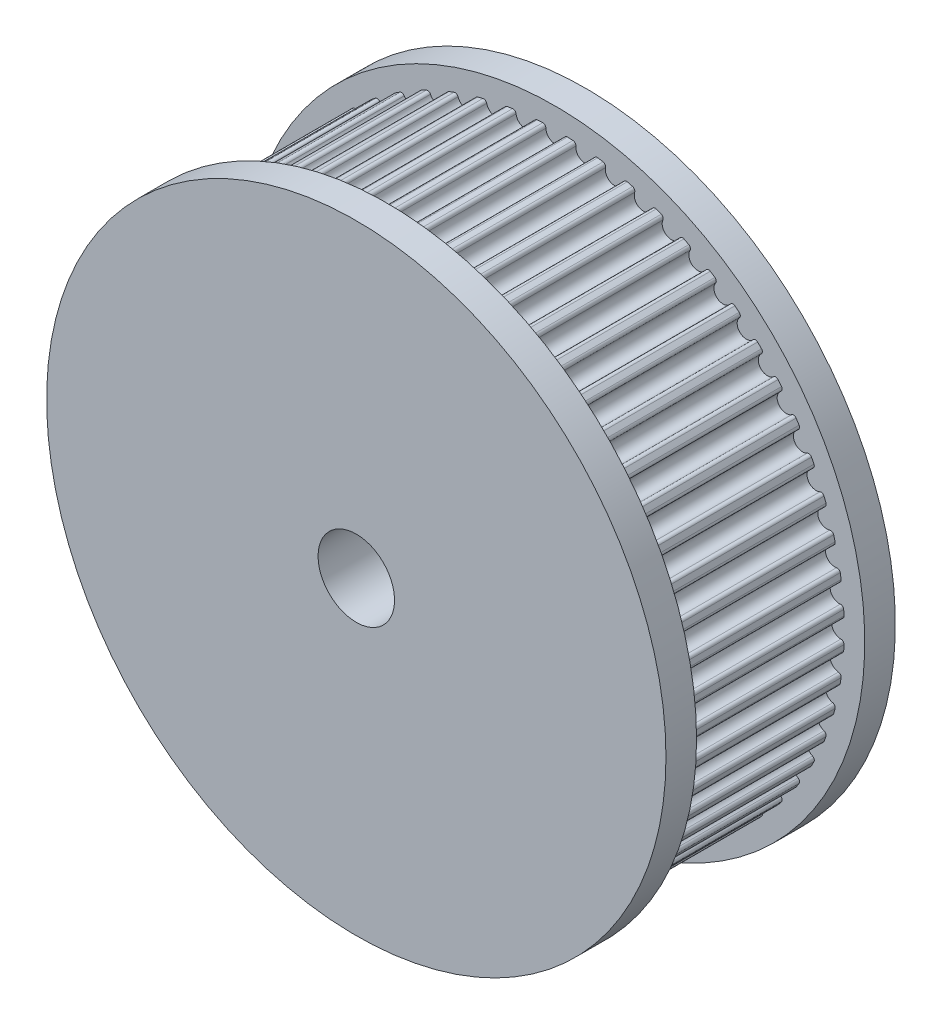
SolidWorks part; units mm, degrees
ref_plane "Front Plane" through (0, 0, 0) normal (0, 0, 1) x (1, 0, 0)
ref_plane "Top Plane" through (0, 0, 0) normal (0, 1, 0) x (1, 0, 0)
ref_plane "Right Plane" through (0, 0, 0) normal (1, 0, 0) x (0, 0, -1)
ref_axis "Axis1" through (0, 0, 55) along (0, 0, -1)
sketch "SketchRevolveGearBelt02" plane through (0, 0, 0) normal (1, 0, 0) x (0, 0, -1)
  line L0 (0, 0) -> (1, 0) construction
  line L1 (5.5, 0) -> (5.5, 18.9081)
  line L2 (5.5, 18.9081) -> (-5.5, 18.9081)
  line L3 (-5.5, 18.9081) -> (-5.5, 0)
  line L4 (-5.5, 0) -> (5.5, 0)
  dimension "GearBeltSide1" = 5.5
  dimension "GearBeltOutsideDiameter" = 18.9081
  dimension "GearBeltSide2" = 5.5
revolve "GearBelt02" add sketch "SketchRevolveGearBelt02" angle 360 about L0
sketch "SketchToothGearBelt02" plane through (0, 0, 0) normal (0, 0, 1) x (1, 0, 0)
  line L0 (-0.8105, 18.8907) -> (0, 21.4481)
  line L1 (0, 21.4481) -> (0.8105, 18.8907)
  arc A0 (0.8105, 18.8907) -> (0.6, 18.6891) centre (0.8018, 18.6891) ccw
  arc A1 (0.6, 18.6891) -> (-0.6, 18.6891) centre (0, 18.6891) cw
  arc A2 (-0.6, 18.6891) -> (-0.8105, 18.8907) centre (-0.8018, 18.6891) ccw
  dimension "GearBeltToothR1" = 0.4036
  dimension "GearBeltToothR2" = 1.2
  dimension "GearBeltToothCapX1" = 0.8105
  dimension "GearBeltToothCapY1" = 2.5574
  dimension "GearBeltToothCapX2" = 0.8105
  dimension "GearBeltToothCapY2" = 2.5574
extrude "ToothExtrudeCutGearBelt02" cut sketch "SketchToothGearBelt02" against normal blind 5.6 and the other way blind 5.6
pattern_circular "PatternGearBelt02" count 60 every 6 about axis through (0, 0, 55) along (0, 0, -1) of "ToothExtrudeCutGearBelt02"
sketch "Sketch5" plane through (0, 0, 5.5) normal (0, 0, 1) x (1, 0, 0)
  circle A0 centre (0, 0) radius 20.25
  dimension "D1" = 40.5
extrude "Boss-Extrude1" add sketch "Sketch5" along normal blind 2
sketch "Sketch6" plane through (0, 0, -5.5) normal (0, 0, -1) x (-1, 0, 0)
  circle A0 centre (0, 0) radius 20.25
  dimension "D1" = 40.5
extrude "Boss-Extrude2" add sketch "Sketch6" along normal blind 2
sketch "Sketch7" plane through (0, 0, -7.5) normal (0, 0, -1) x (-1, 0, 0)
  circle A0 centre (0, 0) radius 10
  dimension "D1" = 20
extrude "Boss-Extrude3" add sketch "Sketch7" along normal blind 7
sketch "Sketch8" plane through (0, 0, -14.5) normal (0, 0, -1) x (-1, 0, 0)
  circle A0 centre (0, 0) radius 2.5
  dimension "D1" = 5
extrude "Cut-Extrude2" cut sketch "Sketch8" against normal through all
